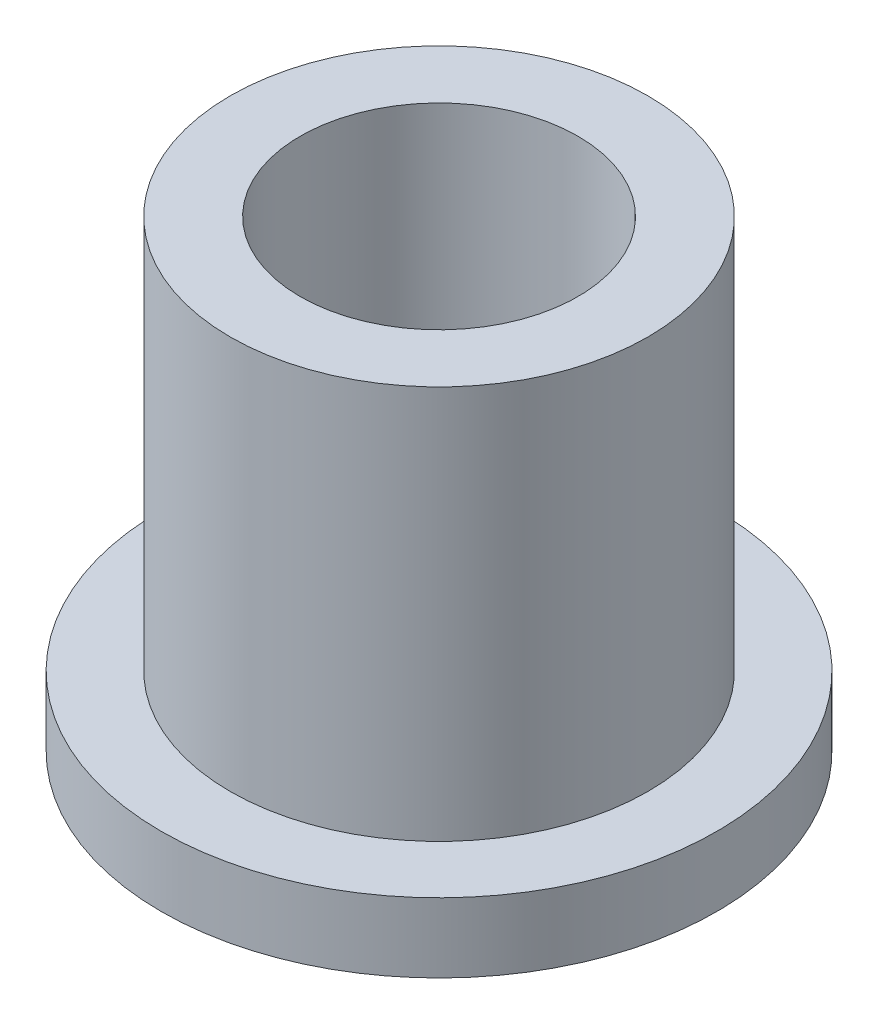
SolidWorks part; units mm, degrees
ref_plane "Front" through (0, 0, 0) normal (0, 0, 1) x (1, 0, 0)
ref_plane "Top" through (0, 0, 0) normal (0, 1, 0) x (1, 0, 0)
ref_plane "Right" through (0, 0, 0) normal (1, 0, 0) x (0, 0, -1)
sketch "Sketch1" plane through (0, 0, 0) normal (0, 1, 0) x (1, 0, 0)
  circle A0 centre (0, 0) radius 3
  circle A1 centre (0, 0) radius 4.51
  circle A2 centre (0, 0) radius 6
  dimension "ID" = 6
  dimension "OD" = 9.02
  dimension "FlangeOD" = 12
sketch "Sketch2" plane through (0, 0, 0) normal (0, 1, 0) x (1, 0, 0)
  circle A0 centre (0, 0) radius 3 construction
  circle A1 centre (0, 0) radius 4.51 construction
  circle A2 centre (0, 0) radius 3
  circle A3 centre (0, 0) radius 4.51
extrude "Boss-Extrude1" add sketch "Sketch2" along normal blind 10
sketch "Sketch3" plane through (0, 0, 0) normal (0, 1, 0) x (1, 0, 0)
  circle A0 centre (0, 0) radius 6 construction
  circle A1 centre (0, 0) radius 4.51 construction
  circle A2 centre (0, 0) radius 6
  circle A3 centre (0, 0) radius 4.51
extrude "Boss-Extrude2" add sketch "Sketch3" along normal blind 1.5
ref_axis "Center Axis 1" through (0, 10, 0) along (0, -1, 0)
